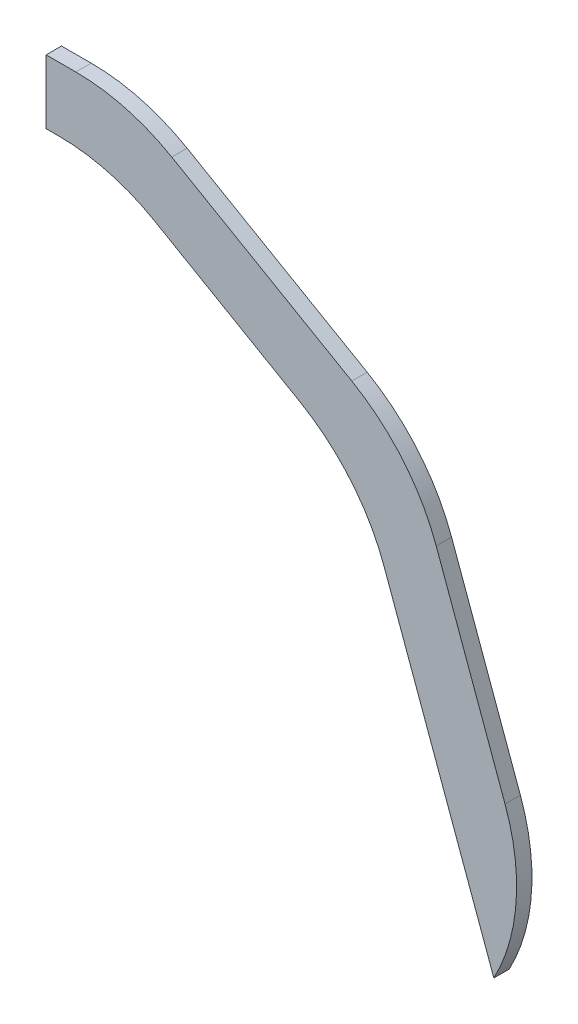
SolidWorks part; units mm, degrees
material "PBT General Purpose"
ref_plane "Front Plane" through (0, 0, 0) normal (0, 0, 1) x (1, 0, 0)
ref_plane "Top Plane" through (0, 0, 0) normal (0, 1, 0) x (1, 0, 0)
ref_plane "Right Plane" through (0, 0, 0) normal (1, 0, 0) x (0, 0, -1)
sketch "Sketch1" plane through (0, 0, 0) normal (0, 0, 1) x (1, 0, 0)
  line L0 (0, 0) -> (1, 0)
  line L1 (1, 0) -> (4.9098, -2.2574)
  line L2 (4.9098, -2.2574) -> (7, -8)
  line L3 (7, -8) -> (7.6527, -6.8695)
  line L4 (7.6527, -6.8695) -> (5.7251, -1.5733)
  line L5 (5.7251, -1.5733) -> (1.2679, 1)
  line L6 (1.2679, 1) -> (0, 1)
  line L7 (0, 1) -> (0, 0)
  point P7 (9.478, -10)
  dimension "D1" = 8
  dimension "D2" = 1
  dimension "D3" = 1
  dimension "D4" = 1
  dimension "D5" = 1
  dimension "D6" = 150
  dimension "D7" = 140
  dimension "D8" = 50
  dimension "D9" = 7
extrude "Boss-Extrude1" add sketch "Sketch1" along normal mid plane 0.24
fillet "Fillet1" radius 3 5 edges at (1.2679, 1, 0) (5.7251, -1.5733, 0) (7.6527, -6.8695, 0) (4.9098, -2.2574, 0) (1, 0, 0)
